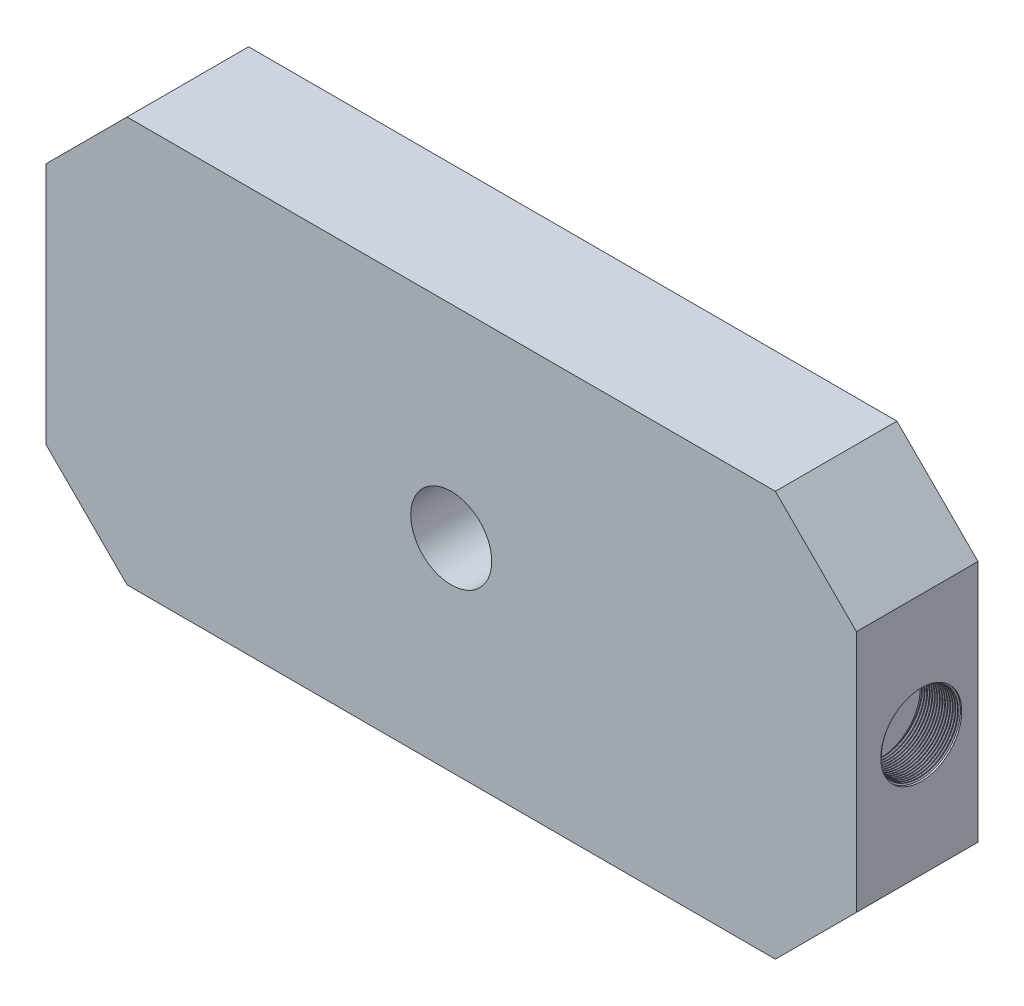
SolidWorks part; units mm, degrees
ref_plane "前视基准面" through (0, 0, 0) normal (0, 0, 1) x (1, 0, 0)
ref_plane "上视基准面" through (0, 0, 0) normal (0, 1, 0) x (1, 0, 0)
ref_plane "右视基准面" through (0, 0, 0) normal (1, 0, 0) x (0, 0, -1)
sketch "草图1" plane through (0, 0, 0) normal (0, 0, 1) x (1, 0, 0)
  line L1 (-104.1352, 30.1303) -> (-4.1352, 30.1303)
  line L2 (-104.1352, 30.1303) -> (-104.1352, -19.8697)
  line L3 (-104.1352, -19.8697) -> (-4.1352, -19.8697)
  line L4 (-4.1352, 30.1303) -> (-4.1352, -19.8697)
  line L5 (-54.1352, -19.8697) -> (-54.1352, 30.1303) construction
  line L6 (-104.1352, 5.1303) -> (-4.1352, 5.1303) construction
  circle A0 centre (-54.1352, 5.1303) radius 5
  point P0 (-54.1352, 5.1303)
  dimension "D1" = 50
  dimension "D2" = 100
extrude "凸台-拉伸1" add sketch "草图1" along normal blind 15
sketch "草图2" plane through (-104.1352, 0, 0) normal (-1, 0, 0) x (0, 0, 1)
  line L0 (0, 30.1303) -> (0, -19.8697) construction
  line L1 (15, -19.8697) -> (0, -19.8697) construction
  circle A0 centre (7, 5.1303) radius 5
  dimension "D1" = 7
  dimension "D2" = 25
extrude "切除-拉伸1" cut sketch "草图2" against normal blind 5 and the other way through all
sketch "草图3" plane through (-4.1352, 0, 0) normal (1, 0, 0) x (0, 0, -1)
  line L0 (0, -19.8697) -> (0, 30.1303) construction
  line L1 (-15, -19.8697) -> (0, -19.8697) construction
  circle A0 centre (-7, 5.1303) radius 5
  dimension "D1" = 7
  dimension "D2" = 25
extrude "切除-拉伸2" cut sketch "草图3" against normal blind 5
chamfer "倒角1" distance 10 angle 45 4 edges at (-104.1352, 30.1303, 7.5) (-104.1352, -19.8697, 7.5) (-4.1352, -19.8697, 7.5) (-4.1352, 30.1303, 7.5)
thread "螺纹线1" pitch 0.3175 method extrude profile "螺纹线轮廓1" start angle 0, offset 0, length 0, pitch 0.3175, diameter 10
ref_plane "基准面1" through (-104.1352, 5.1303, 2) normal (0, -1, 0) x (0, 0, -1)
sketch "螺纹线轮廓1" plane through (-104.1352, 5.1303, 2) normal (0, -1, 0) x (0, 0, -1)
  line L0 (0, 0) -> (0, 0.3175) construction
  line L11 (0, 0) -> (0, 0.2778)
  line L12 (0, 0.2778) -> (-0.1719, 0.1786)
  line L13 (-0.1719, 0.1786) -> (-0.1719, 0.0992)
  line L15 (-0.1719, 0.0992) -> (0, 0)
  line L17 (-0.1719, 0.1389) -> (0, 0.1389) construction
  point P2 (0, 0)
  dimension "Pitch" = 0.3175
  dimension "Profile_Angle" = 60
  dimension "Profile_Land" = 0.0794
  dimension "Profile_Height" = 0.1719
thread "螺纹线2" pitch 0.3175 method extrude profile "螺纹线轮廓2" start angle 0, offset 0, length 0, pitch 0.3175, diameter 10
ref_plane "基准面2" through (-4.1352, 5.1303, 12) normal (0, -1, 0) x (0, 0, 1)
sketch "螺纹线轮廓2" plane through (-4.1352, 5.1303, 12) normal (0, -1, 0) x (0, 0, 1)
  line L0 (0, 0) -> (0, 0.3175) construction
  line L11 (0, 0) -> (0, 0.2778)
  line L12 (0, 0.2778) -> (-0.1719, 0.1786)
  line L13 (-0.1719, 0.1786) -> (-0.1719, 0.0992)
  line L15 (-0.1719, 0.0992) -> (0, 0)
  line L17 (-0.1719, 0.1389) -> (0, 0.1389) construction
  point P2 (0, 0)
  dimension "Pitch" = 0.3175
  dimension "Profile_Angle" = 60
  dimension "Profile_Land" = 0.0794
  dimension "Profile_Height" = 0.1719
